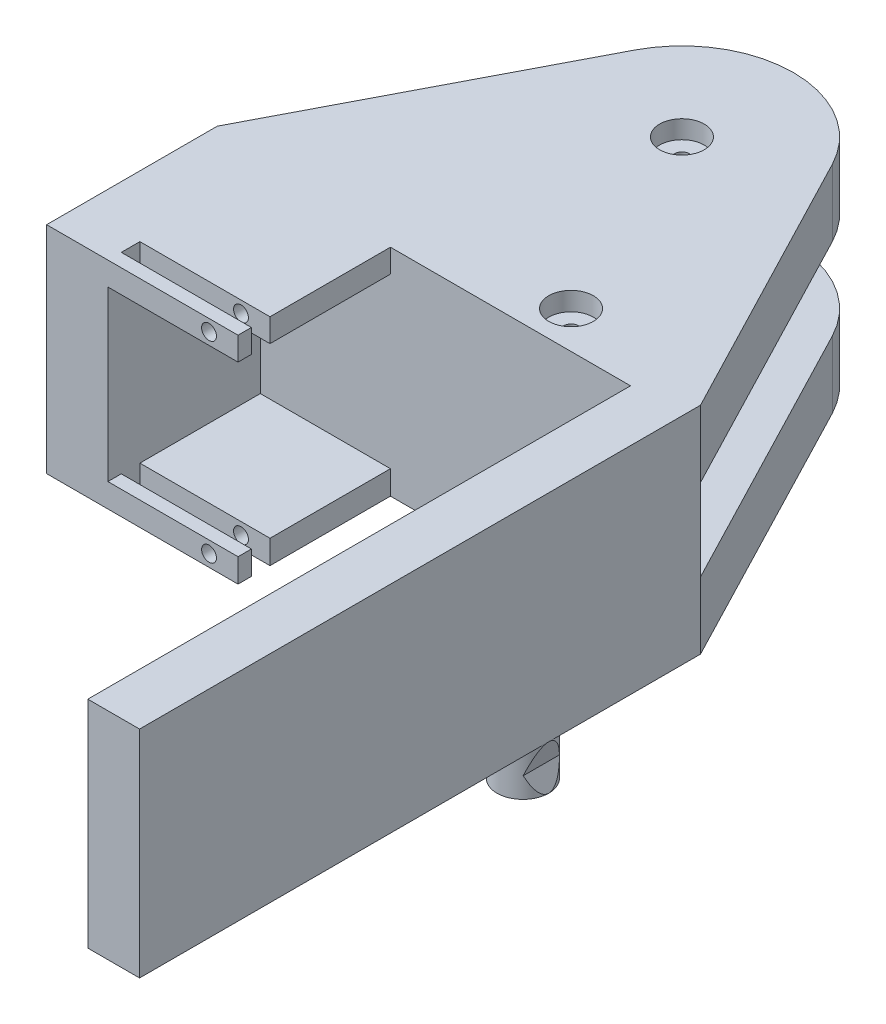
SolidWorks part; units mm, degrees
material "ABS"
ref_plane "Front Plane" through (0, 0, 0) normal (0, 0, 1) x (1, 0, 0)
ref_plane "Top Plane" through (0, 0, 0) normal (0, 1, 0) x (1, 0, 0)
ref_plane "Right Plane" through (0, 0, 0) normal (1, 0, 0) x (0, 0, -1)
sketch "Sketch1" plane through (0, 0, 0) normal (0, 0, 1) x (1, 0, 0)
  line L0 (0, 11) -> (65, 11)
  line L1 (0, 0) -> (65, 0)
  line L2 (0, 0) -> (0, 65)
  line L3 (0, 65) -> (65, 65)
  line L4 (65, 0) -> (65, 65)
  line L5 (0, 0) -> (65, 0)
  line L6 (0, 0) -> (0, 10)
  line L7 (0, 10) -> (65, 10)
  line L8 (65, 0) -> (65, 10)
  line L9 (0, 10) -> (65, 10)
  line L10 (0, 10) -> (0, 20)
  line L11 (0, 20) -> (65, 20)
  line L12 (65, 10) -> (65, 20)
  line L13 (65, 20) -> (0, 20)
  line L14 (65, 20) -> (65, 30)
  line L15 (65, 30) -> (0, 30)
  line L16 (0, 20) -> (0, 30)
  line L17 (0, 30) -> (65, 30)
  line L18 (0, 30) -> (0, 40)
  line L19 (0, 40) -> (65, 40)
  line L20 (65, 30) -> (65, 40)
  line L21 (0, 31) -> (65, 31)
  line L22 (36.97, 30) -> (36.97, 31) construction
  line L23 (37.8533, 10) -> (37.8533, 11) construction
  dimension "D1" = 65
  dimension "D2" = 65
  dimension "D3" = 10
  dimension "D4" = 1
extrude "Boss-Extrude1" add sketch "Sketch1" along normal blind 45 contours L11 L2 L7 L4 | L19 L2 L15 L4 region at (32.5, 15.5, 0) region at (32.5, 35.5, 0)
sketch "Sketch2" plane through (0, 10, 0) normal (0, -1, 0) x (1, 0, 0)
  line L0 (32.5, 0) -> (32.5, 45) construction
  line L3 (0, 45) -> (19.1907, 8.0816)
  line L4 (65, 45) -> (45.8093, 8.0816)
  line L5 (0, 45) -> (0, 0)
  line L6 (0, 0) -> (65, 0)
  line L7 (65, 0) -> (65, 45)
  circle A0 centre (32.5, 15) radius 15
  circle A1 centre (32.5, 15) radius 1
  dimension "D1" = 30
  dimension "D2" = 2
  dimension "D3" = 65
  dimension "D4" = 45
extrude "Cut-Extrude5" cut sketch "Sketch2" against normal blind 34 contours A0 L6 L4 | L0 A1 | A1 L0 | A1 region at (56.7767, 10, 14.6593) region at (32.0756, 10, 15) region at (32.9244, 10, 15)
extrude "Cut-Extrude6" cut sketch "Sketch2<6>" against normal blind 34 contours A0 L3 region at (8.2233, 10, 14.6593)
sketch "Sketch2<6>" plane through (0, 10, 0) normal (0, -1, 0) x (1, 0, 0) same geometry as "Sketch2"
sketch "Sketch3" plane through (0, 40, 0) normal (0, 1, 0) x (1, 0, 0)
  circle A0 centre (32.5, -15) radius 3
  dimension "D1" = 6
extrude "Cut-Extrude7" cut sketch "Sketch3" against normal blind 2.45
sketch "Sketch4" plane through (0, 20, 0) normal (0, 1, 0) x (1, 0, 0)
  circle A0 centre (32.5, -15) radius 3
extrude "Cut-Extrude8" cut sketch "Sketch4" against normal blind 2.45
sketch "Sketch5" plane through (0, 0, 45) normal (0, 0, 1) x (1, 0, 0)
  line L1 (0, 11) -> (65, 11)
  line L2 (0, 11) -> (0, 40)
  line L3 (0, 40) -> (65, 40)
  line L4 (65, 11) -> (65, 40)
extrude "Boss-Extrude2" add sketch "Sketch5" along normal blind 2.45
sketch "Sketch6" plane through (0, 11, 0) normal (0, -1, 0) x (1, 0, 0)
  line L0 (32.5, 15) -> (32.5, 26.7) construction
  line L1 (29, 26.7) -> (36, 26.7)
  line L2 (29, 26.7) -> (29, 33.5539)
  line L3 (29, 33.5539) -> (36, 33.5539)
  line L4 (36, 26.7) -> (36, 33.5539)
  line L5 (32.5, 26.7) -> (32.5, 28.3) construction
  circle A0 centre (32.5, 15) radius 11.5
  circle A1 centre (32.5, 28.3) radius 0.75
  dimension "D1" = 23
  dimension "D2" = 1.5
  dimension "D3" = 7
  dimension "D4" = 1.6
  dimension "D5" = 11.7
extrude "Boss-Extrude3" add sketch "Sketch6" along normal blind 3.35 contours L1 L4 L3 L2 region at (32.5, 11, 30.1968)
sketch "Sketch7" plane through (0, 7.65, 0) normal (0, -1, 0) x (1, 0, 0)
  line L0 (29, 29.7) -> (29, 26.7)
  line L1 (29, 26.7) -> (29, 33.5539) construction
  line L2 (29, 26.7) -> (36, 26.7) construction
  line L3 (29, 26.7) -> (31, 26.7)
  line L4 (31, 26.7) -> (29, 29.7)
  line L5 (34, 26.7) -> (36, 29.7)
  line L6 (36, 26.7) -> (36, 33.5539) construction
  line L7 (36, 29.7) -> (36, 26.7)
  line L8 (36, 26.7) -> (34, 26.7)
  dimension "D1" = 2
  dimension "D2" = 3
extrude "Cut-Extrude9" cut sketch "Sketch7" against normal blind 3.35
sketch "Sketch8" plane through (0, 7.65, 0) normal (0, -1, 0) x (1, 0, 0)
  line L0 (32.5, 33.5539) -> (32.5, 30.1922) construction
  line L1 (29, 33.5539) -> (36, 33.5539) construction
  line L2 (30.4549, 30.3333) -> (30.2789, 27.7817)
  line L3 (31, 26.7) -> (29, 29.7) construction
  line L4 (34.5451, 30.3333) -> (34.7211, 27.7817)
  line L5 (36, 29.7) -> (34, 26.7) construction
  line L7 (29.45, 30.2005) -> (29.4468, 29.0297)
  line L8 (35.55, 30.2005) -> (35.5532, 29.0297)
  line L9 (30.2789, 27.7817) -> (31, 26.7) construction
  line L10 (34.7211, 27.7817) -> (34, 26.7) construction
  line L11 (30.2789, 27.7817) -> (29.4468, 29.0297) construction
  line L12 (35.5532, 29.0297) -> (34.7211, 27.7817) construction
  circle A0 centre (32.5, 30.1922) radius 2.05
  circle A1 centre (32.5, 30.1922) radius 3.05
  line M1 (29, 29.7) -> (31, 26.7)
  line M3 (34, 26.7) -> (36, 29.7)
  line M4 (36, 29.7) -> (36, 33.5539)
  line M5 (36, 33.5539) -> (29, 33.5539)
  line M6 (29, 33.5539) -> (29, 29.7)
  dimension "D1" = 4.1
  dimension "D3" = 1
  dimension "D2" = 3.3617
  dimension "D4" = 1.3
  dimension "D5" = 1.5
extrude "Boss-Extrude4" add sketch "Sketch8" along normal blind 2 contours A1 L8 L7 M3 M4 M5 M6 M1 | L4 A1 L2 A0 | A1 L7 L2 M1 | A1 L4 L8 M3 region at (30.2975, 7.65, 29.2123) region at (29.7908, 7.65, 28.7274) region at (29.3651, 7.65, 29.6153) region at (35.2092, 7.65, 28.7274)
sketch "Sketch9" plane through (0, 0, 47.45) normal (0, 0, 1) x (1, 0, 0)
  line L0 (65, 40) -> (0, 40) construction
  line L1 (65, 11) -> (58.0376, 11)
  line L2 (65, 11) -> (65, 40)
  line L3 (65, 40) -> (58.0376, 40)
  line L4 (58.0376, 11) -> (58.0376, 40)
extrude "Boss-Extrude5" add sketch "Sketch9" along normal blind 73
sketch "Sketch10" plane through (0, 11, 0) normal (0, -1, 0) x (1, 0, 0)
  line L0 (45.0376, 42.45) -> (45.0376, 47.45) construction
  line L1 (0, 47.45) -> (58.0376, 47.45) construction
  line L2 (58.0376, 120.45) -> (58.0376, 47.45) construction
  circle A0 centre (45.0376, 42.45) radius 3
  dimension "D1" = 6
  dimension "D2" = 13
  dimension "D3" = 5
extrude "Cut-Extrude10" cut sketch "Sketch10" against normal blind 2.5
sketch "Sketch11" plane through (0, 40, 0) normal (0, 1, 0) x (1, 0, 0)
  line L0 (45.0376, -42.45) -> (45.0376, -47.45) construction
  line L1 (58.0376, -47.45) -> (0, -47.45) construction
  line L2 (58.0376, -120.45) -> (58.0376, -47.45) construction
  circle A0 centre (45.0376, -42.45) radius 3
  dimension "D1" = 6
  dimension "D2" = 5
  dimension "D3" = 13
extrude "Cut-Extrude11" cut sketch "Sketch11" against normal blind 2.5
sketch "Sketch12" plane through (0, 37.5, 0) normal (0, 1, 0) x (1, 0, 0)
  circle A0 centre (45.0376, -42.45) radius 1
extrude "Cut-Extrude12" cut sketch "Sketch12" against normal blind 32.5
sketch "Sketch13" plane through (0, 0, 47.45) normal (0, 0, 1) x (1, 0, 0)
  line L0 (0, 11) -> (58.0376, 11) construction
  line L1 (25.7437, 11) -> (0, 11)
  line L2 (25.7437, 11) -> (25.7437, 40)
  line L3 (25.7437, 40) -> (0, 40)
  line L4 (0, 11) -> (0, 40)
extrude "Boss-Extrude6" add sketch "Sketch13" along normal blind 20.5
sketch "Sketch14" plane through (25.7437, 0, 0) normal (1, 0, 0) x (0, 0, -1)
  line L0 (-47.45, 11) -> (-47.45, 40) construction
  line L1 (-47.45, 9.15) -> (-63.65, 9.15)
  line L2 (-47.45, 9.15) -> (-47.45, 41.85)
  line L3 (-47.45, 41.85) -> (-63.65, 41.85)
  line L4 (-63.65, 9.15) -> (-63.65, 41.85)
  line L5 (-63.65, 25.5) -> (-67.95, 25.5) construction
  line L6 (-67.95, 11) -> (-67.95, 40) construction
  dimension "D1" = 16.2
  dimension "D2" = 32.7
extrude "Cut-Extrude13" cut sketch "Sketch14" against normal blind 17.5
sketch "Sketch16" plane through (8.2437, 0, 0) normal (1, 0, 0) x (0, 0, -1)
  line L0 (-47.45, 11) -> (-47.45, 40) construction
  line L1 (-63.65, 11) -> (-47.45, 11)
  line L2 (-63.65, 11) -> (-63.65, 14.1979)
  line L3 (-63.65, 14.1979) -> (-47.45, 14.1979)
  line L4 (-47.45, 11) -> (-47.45, 14.1979)
  line L5 (-63.65, 40) -> (-47.45, 40)
  line L6 (-63.65, 40) -> (-63.65, 36.8625)
  line L7 (-63.65, 36.8625) -> (-47.45, 36.8625)
  line L8 (-47.45, 40) -> (-47.45, 36.8625)
extrude "Boss-Extrude7" add sketch "Sketch16" along normal blind 17.5
sketch "Sketch17" plane through (25.7437, 0, 0) normal (1, 0, 0) x (0, 0, -1)
  line L0 (-63.65, 36.8625) -> (-47.45, 36.8625) construction
  line L1 (-67.95, 11) -> (-66.15, 11)
  line L2 (-67.95, 11) -> (-67.95, 14.1979)
  line L3 (-67.95, 14.1979) -> (-66.15, 14.1979)
  line L4 (-66.15, 11) -> (-66.15, 14.1979)
  line L5 (-67.95, 40) -> (-66.15, 40)
  line L6 (-67.95, 40) -> (-67.95, 36.8625)
  line L7 (-67.95, 36.8625) -> (-66.15, 36.8625)
  line L8 (-66.15, 40) -> (-66.15, 36.8625)
  line L9 (-47.45, 14.1979) -> (-63.65, 14.1979) construction
  line L10 (-63.65, 14.1979) -> (-63.65, 36.8625) construction
  line L12 (-67.95, 36.8625) -> (-63.65, 36.8625)
  line L13 (-67.95, 36.8625) -> (-67.95, 14.1979)
  line L14 (-67.95, 14.1979) -> (-63.65, 14.1979)
  line L15 (-63.65, 36.8625) -> (-63.65, 14.1979)
  line L16 (-63.65, 14.1979) -> (-66.15, 14.1979)
  line L17 (-63.65, 14.1979) -> (-63.65, 11)
  line L18 (-63.65, 11) -> (-66.15, 11)
  line L19 (-66.15, 14.1979) -> (-66.15, 11)
  line L20 (-63.65, 36.8625) -> (-66.15, 36.8625)
  line L21 (-63.65, 36.8625) -> (-63.65, 40)
  line L22 (-63.65, 40) -> (-66.15, 40)
  line L23 (-66.15, 36.8625) -> (-66.15, 40)
  line M4 (-67.95, 11) -> (-47.45, 11)
  line M7 (-63.65, 14.1979) -> (-63.65, 36.8625)
  line M10 (-47.45, 40) -> (-67.95, 40)
  line M11 (-67.95, 40) -> (-67.95, 11)
  dimension "D1" = 2.5
extrude "Cut-Extrude14" cut sketch "Sketch17" against normal blind 17.5 contours L3 L14 L12 L7 M7 M11 | L17 L14 L4 M4 | L12 L21 L8 M10 region at (25.7437, 12.5989, 64.9) region at (25.7437, 25.5302, 65.8) region at (25.7437, 38.4312, 64.9)
sketch "Sketch19" plane through (0, 0, 67.95) normal (0, 0, 1) x (1, 0, 0)
  line L1 (8.2437, 36.8625) -> (8.2437, 14.1979) construction
  line L2 (21.8437, 38.4312) -> (25.7437, 38.4312) construction
  line L3 (25.7437, 36.8625) -> (25.7437, 40) construction
  line L4 (21.8437, 12.5989) -> (25.7437, 12.5989) construction
  line L5 (25.7437, 11) -> (25.7437, 14.1979) construction
  circle A0 centre (21.8437, 12.5989) radius 1
  circle A1 centre (21.8437, 38.4312) radius 1
  dimension "D1" = 2
  dimension "D2" = 12.6
  dimension "D3" = 12.6
extrude "Cut-Extrude15" cut sketch "Sketch19" against normal blind 10
sketch "Sketch20" plane through (0, 11, 0) normal (0, -1, 0) x (1, 0, 0)
  line L0 (65, 65.4111) -> (58.0376, 65.4111) construction
  line L1 (65, 120.45) -> (65, 45) construction
  line L2 (58.0376, 120.45) -> (58.0376, 47.45) construction
  circle A0 centre (61.5188, 65.4111) radius 3.4812
extrude "Boss-Extrude8" add sketch "Sketch20" along normal blind 6
sketch "Sketch22" plane through (0, 0, 120.45) normal (0, 0, 1) x (1, 0, 0)
  line L0 (65, 11) -> (65, 40) construction
  line L1 (65, 14.9198) -> (58.0376, 14.9198)
  line L2 (65, 14.9198) -> (65, 5)
  line L3 (65, 5) -> (58.0376, 5)
  line L4 (58.0376, 14.9198) -> (58.0376, 5)
  line L5 (58.0376, 40) -> (58.0376, 11) construction
  line L6 (58.0376, 5) -> (65, 5) construction
  line L7 (65, 5) -> (64, 7.7559)
  line L8 (64, 7.7559) -> (65, 11)
  line L9 (64, 7.7559) -> (65, 7.7559) construction
  dimension "D1" = 1
extrude "Cut-Extrude17" cut sketch "Sketch22" against normal blind 66 contours L8 L9 L2 | L9 L7 L2 region at (64.6667, 8.8372, 120.45) region at (64.6667, 6.8372, 120.45)
